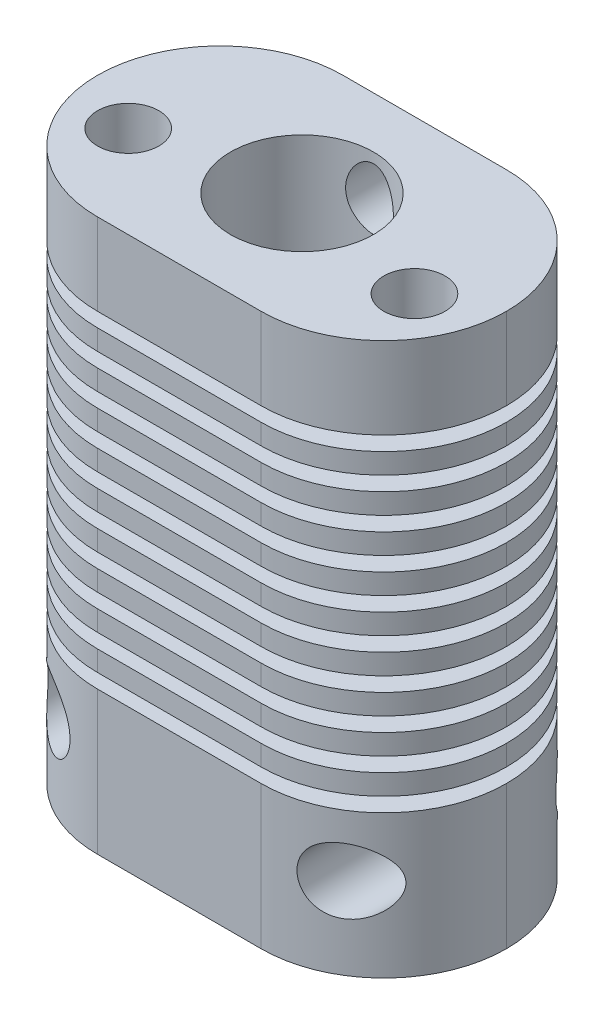
SolidWorks part; units mm, degrees
ref_plane "Płaszczyzna przednia" through (0, 0, 0) normal (0, 0, 1) x (1, 0, 0)
ref_plane "Płaszczyzna górna" through (0, 0, 0) normal (0, 1, 0) x (1, 0, 0)
ref_plane "Płaszczyzna prawa" through (0, 0, 0) normal (1, 0, 0) x (0, 0, -1)
sketch "Szkic1" plane through (0, 0, 0) normal (0, 0, 1) x (1, 0, 0)
  line L1 (0, 0) -> (20, 0)
  line L2 (0, 0) -> (0, 27)
  line L3 (0, 27) -> (20, 27)
  line L4 (20, 0) -> (20, 27)
  dimension "D1" = 27
  dimension "D2" = 20
extrude "Dodanie-wyciągnięcie1" add sketch "Szkic1" along normal blind 12
fillet "Zaokrąglenie2" radius 6 4 edges at (20, 13.5, 0) (20, 13.5, 12) (0, 13.5, 0) (0, 13.5, 12)
ref_plane "Płaszczyzna1" through (10, 0, 0) normal (-1, 0, 0) x (0, 0, 1)
ref_plane "Plane1" through (10, 0, 0) normal (-1, 0, 0) x (0, 0, 1)
sketch "Sketch1" plane through (10, 0, 0) normal (-1, 0, 0) x (0, 0, 1)
  line L0 (0, 27) -> (0, 0)
  line L1 (12, 27) -> (12, 0)
  line L2 (0, 27) -> (12, 27)
  line L3 (12, 0) -> (0, 0)
  line L4 (12, 0) -> (0, 0)
  line L5 (0, 27) -> (12, 27)
  line L6 (12, 27) -> (12, 0)
  line L7 (0, 27) -> (0, 0)
ref_plane "Plane2" through (0, 0, 0) normal (-1, 0, 0) x (0, 0, 1)
sketch "Sketch2" plane through (0, 0, 0) normal (-1, 0, 0) x (0, 0, 1)
  line L0 (6, 0) -> (6, 27)
  line L1 (6, 0) -> (6, 27)
sketch "Sketch3" plane through (10, 0, 0) normal (-1, 0, 0) x (0, 0, 1)
  line L0 (0, 27) -> (12, 27) construction
  line L1 (-4.7141, 23) -> (1.7, 23)
  line L2 (-4.7141, 23) -> (-4.7141, 22.3)
  line L3 (-4.7141, 22.3) -> (1.7, 22.3)
  line L4 (1.7, 23) -> (1.7, 22.3)
  line L5 (6, 0) -> (6, 27) construction
  line L6 (-4.7141, 21.3) -> (-4.7141, 20.6)
  line L7 (-4.7141, 21.3) -> (1.7, 21.3)
  line L8 (1.7, 21.3) -> (1.7, 20.6)
  line L9 (-4.7141, 20.6) -> (1.7, 20.6)
  line L10 (-4.7141, 19.6) -> (-4.7141, 18.9)
  line L11 (-4.7141, 19.6) -> (1.7, 19.6)
  line L12 (1.7, 19.6) -> (1.7, 18.9)
  line L13 (-4.7141, 18.9) -> (1.7, 18.9)
  line L14 (-4.7141, 17.9) -> (-4.7141, 17.2)
  line L15 (-4.7141, 17.9) -> (1.7, 17.9)
  line L16 (1.7, 17.9) -> (1.7, 17.2)
  line L17 (-4.7141, 17.2) -> (1.7, 17.2)
  line L18 (-4.7141, 16.2) -> (-4.7141, 15.5)
  line L19 (-4.7141, 16.2) -> (1.7, 16.2)
  line L20 (1.7, 16.2) -> (1.7, 15.5)
  line L21 (-4.7141, 15.5) -> (1.7, 15.5)
  line L22 (-4.7141, 14.5) -> (-4.7141, 13.8)
  line L23 (-4.7141, 14.5) -> (1.7, 14.5)
  line L24 (1.7, 14.5) -> (1.7, 13.8)
  line L25 (-4.7141, 13.8) -> (1.7, 13.8)
  line L26 (-4.7141, 12.8) -> (-4.7141, 12.1)
  line L27 (-4.7141, 12.8) -> (1.7, 12.8)
  line L28 (1.7, 12.8) -> (1.7, 12.1)
  line L29 (-4.7141, 12.1) -> (1.7, 12.1)
  line L30 (-4.7141, 11.1) -> (-4.7141, 10.4)
  line L31 (-4.7141, 11.1) -> (1.7, 11.1)
  line L32 (1.7, 11.1) -> (1.7, 10.4)
  line L33 (-4.7141, 10.4) -> (1.7, 10.4)
  line L34 (-4.7141, 9.4) -> (-4.7141, 8.7)
  line L35 (-4.7141, 9.4) -> (1.7, 9.4)
  line L36 (1.7, 9.4) -> (1.7, 8.7)
  line L37 (-4.7141, 8.7) -> (1.7, 8.7)
  line L38 (-4.7141, 7.7) -> (-4.7141, 7)
  line L39 (-4.7141, 7.7) -> (1.7, 7.7)
  line L40 (1.7, 7.7) -> (1.7, 7)
  line L41 (-4.7141, 7) -> (1.7, 7)
  line L42 (6, 26.2556) -> (6, -0.7641) construction
  dimension "D1" = 4
  dimension "D2" = 4.3
  dimension "D3" = 0.7
  dimension "D5" = 4.3
  dimension "D4" = 10
revolve "Cut-Revolve1" cut sketch "Sketch3" angle 360 about L42
hole_wizard "Ø3.0mm Dowel Hole2" positions "Sketch5" profile "Sketch7" hole size "Ø3.0" standard "ANSI Metric"
sketch "Sketch5" plane through (0, 0, 0) normal (0, 0, -1) x (-1, 0, 0)
  line L1 (-10, 27) -> (-10, 0) construction
  line L2 (-14, 27) -> (-6, 27) construction
  line L3 (-14, 27) -> (-14, 23) construction
  point P4 (-10, 25)
  dimension "D1" = 2
  dimension "D2" = 4
sketch "Sketch7" plane through (10, 25, 0) normal (1, 0, 0) x (0, 1, 0)
  line L0 (0, 0) -> (0, 3.4013)
  line L1 (0, 3.4013) -> (1.5, 2.5)
  line L2 (1.5, 2.5) -> (1.5, 0)
  line L5 (1.5, 0) -> (0, 0)
  line L10 (0, 3.4013) -> (-1.5, 2.5) construction
  line L11 (0, -6.35) -> (0, 107.95) construction
  dimension "Hole Dia." = 3
  dimension "Hole Depth" = 2.5
  dimension "Drill Angle" = 118
hole_wizard "Ø3.0mm Dowel Hole3" positions "3DSketch1" profile "Sketch8" hole size "Ø3.0" standard "ANSI Metric" end condition through all
sketch3d "3DSketch1"
  line L1 (10, 27, 0) -> (10, 0, 0) construction
  line L2 (6, 0, 0) -> (14, 0, 0) construction
  point P0 (17.15, 4, 0)
  point P2 (2.85, 4, 0)
  dimension "D1" = 14.3
  dimension "D2" = 7.15
  dimension "D3" = 4
sketch "Sketch8" plane through (17.15, 4, 0) normal (1, 0, 0) x (0, 1, 0)
  line L0 (0, 0) -> (0, 12)
  line L1 (0, 12) -> (1.6, 12)
  line L2 (1.6, 12) -> (1.6, 0)
  line L5 (1.6, 0) -> (0, 0)
  line L11 (0, -6.35) -> (0, 107.95) construction
  dimension "Thru Hole Dia." = 3.2
  dimension "Thru Hole Depth" = 12
hole_wizard "Ø6.0mm Dowel Hole1" positions "Sketch9" profile "Sketch10" hole size "Ø6.0" standard "ANSI Metric"
sketch "Sketch9" plane through (0, 27, 0) normal (0, 1, 0) x (1, 0, 0)
  line L0 (14, -12) -> (6, -12) construction
  point P0 (10, -6)
  dimension "D1" = 6
  dimension "D2" = 10
sketch "Sketch10" plane through (10, 27, 6) normal (1, 0, 0) x (0, 0, 1)
  line L0 (0, 0) -> (0, 16.6)
  line L1 (0, 16.6) -> (3.5, 16.6)
  line L2 (3.5, 16.6) -> (3.5, 0)
  line L5 (3.5, 0) -> (0, 0)
  line L10 (0, 16.6) -> (-3.5, 16.6) construction
  line L11 (0, -6.35) -> (0, 107.95) construction
  dimension "Hole Dia." = 7
  dimension "Hole Depth" = 16.6
  dimension "Drill Angle" = 180
hole_wizard "Ø3.0mm Dowel Hole4" positions "Sketch11" profile "Sketch12" hole size "Ø3.0" standard "ANSI Metric"
sketch "Sketch11" plane through (0, 27, 0) normal (0, 1, 0) x (1, 0, 0)
  line L0 (10, 0) -> (10, -12) construction
  circle A0 centre (10, -6) radius 3.5 construction
  point P0 (17, -7.5)
  point P2 (3, -7.5)
  dimension "D1" = 14
  dimension "D2" = 1.5
  dimension "D3" = 7
sketch "Sketch12" plane through (17, 27, 7.5) normal (1, 0, 0) x (0, 0, 1)
  line L0 (0, 0) -> (0, 3.9013)
  line L1 (0, 3.9013) -> (1.5, 3)
  line L2 (1.5, 3) -> (1.5, 0)
  line L5 (1.5, 0) -> (0, 0)
  line L10 (0, 3.9013) -> (-1.5, 3) construction
  line L11 (0, -6.35) -> (0, 107.95) construction
  dimension "Hole Dia." = 3
  dimension "Hole Depth" = 3
  dimension "Drill Angle" = 118
hole_wizard "Ø5.0mm Dowel Hole1" positions "Sketch13" profile "Sketch14" hole size "Ø5.0" standard "ANSI Metric" end condition through all
sketch "Sketch13" plane through (0, 10.4, 0) normal (0, 1, 0) x (1, 0, 0)
  circle A1 centre (10, -6) radius 3.5 construction
  point P0 (10, -6)
sketch "Sketch14" plane through (10, 10.4, 6) normal (1, 0, 0) x (0, 0, 1)
  line L0 (0, 0) -> (0, 10.4)
  line L1 (0, 10.4) -> (2.5, 10.4)
  line L2 (2.5, 10.4) -> (2.5, 0)
  line L5 (2.5, 0) -> (0, 0)
  line L11 (0, -6.35) -> (0, 107.95) construction
  dimension "Thru Hole Dia." = 5
  dimension "Thru Hole Depth" = 10.4
hole_wizard "Ø10.0mm Dowel Hole3" positions "Sketch15" profile "Sketch16" hole size "Ø10.0" standard "ANSI Metric"
sketch "Sketch15" plane through (0, 0, 0) normal (0, -1, 0) x (-1, 0, 0)
  line L0 (-10, -12) -> (-10, 0) construction
  line L1 (-6, 0) -> (-14, 0) construction
  point P0 (-10, -6)
  dimension "D1" = 6
sketch "Sketch16" plane through (10, 0, 6) normal (1, 0, 0) x (0, 0, -1)
  line L0 (0, 0) -> (0, 9.0043)
  line L1 (0, 9.0043) -> (5, 6)
  line L2 (5, 6) -> (5, 0)
  line L5 (5, 0) -> (0, 0)
  line L10 (0, 9.0043) -> (-5, 6) construction
  line L11 (0, -6.35) -> (0, 107.95) construction
  dimension "Hole Dia." = 10
  dimension "Hole Depth" = 6
  dimension "Drill Angle" = 118
